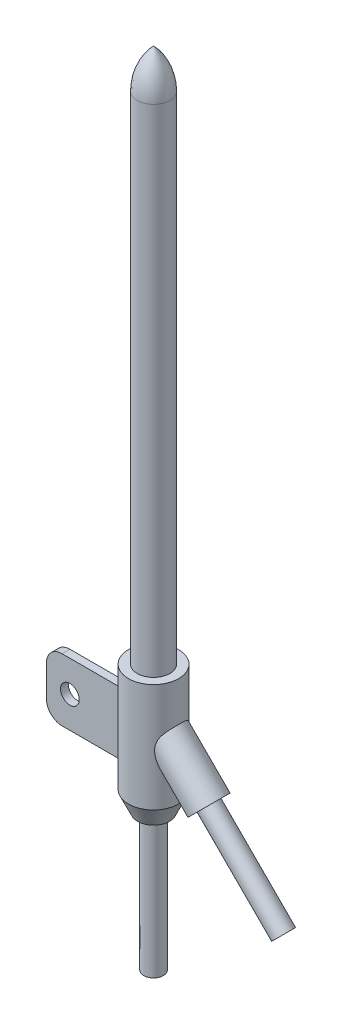
SolidWorks part; units mm, degrees
ref_plane "Front Plane" through (0, 0, 0) normal (0, 0, 1) x (1, 0, 0)
ref_plane "Top Plane" through (0, 0, 0) normal (0, 1, 0) x (1, 0, 0)
ref_plane "Right Plane" through (0, 0, 0) normal (1, 0, 0) x (0, 0, -1)
sketch "Sketch2" plane through (0, 0, 0) normal (0, 1, 0) x (1, 0, 0)
  circle A0 centre (0, 0) radius 2.085
  dimension "D1" = 4.17
extrude "Boss-Extrude1" add sketch "Sketch2" along normal blind 63.5
sketch "Sketch3" plane through (0, 0, 0) normal (0, 0, 1) x (1, 0, 0)
  line L0 (2.085, 63.5) -> (2.085, 60.967) construction
  line L1 (2.085, 0) -> (2.085, 63.5) construction
  line L2 (0, 63.5) -> (0, 68.5)
  line L3 (2.085, 63.5) -> (-2.085, 63.5) construction
  line L4 (2.085, 63.5) -> (0, 63.5)
  arc A0 (2.085, 63.5) -> (0, 68.5) centre (-4.9527, 63.5) ccw
  dimension "D1" = 5
revolve "Revolve2" add sketch "Sketch3" angle 360 about L2
sketch "Sketch4" plane through (0, 0, 0) normal (0, 0, 1) x (1, 0, 0)
  line L0 (0, 0) -> (0, -16.4)
  line L1 (0, -16.4) -> (2.05, -16.4)
  line L2 (2.05, -16.4) -> (3.21, -13.9)
  line L3 (3.21, -13.9) -> (3.21, 0)
  line L4 (3.21, 0) -> (0, 0)
  line L5 (0, 0) -> (0, -13.3708) construction
  dimension "D1" = 6.42
  dimension "D2" = 4.1
  dimension "D3" = 2.5
  dimension "D4" = 16.4
revolve "Revolve3" add sketch "Sketch4" angle 360 about L5
sketch "Sketch5" plane through (0, 0, 0) normal (0, 0, 1) x (1, 0, 0)
  line L0 (0, 0) -> (0, -16.4) construction
  line L1 (-2.05, -16.4) -> (2.05, -16.4) construction
  line L2 (0, -8.2) -> (3.21, -8.2) construction
  line L3 (3.21, -13.9) -> (3.21, 0) construction
  line L4 (0, -8.2) -> (-3.21, -8.2) construction
  line L5 (-3.21, 0) -> (-3.21, -13.9) construction
  point P13 (-3.21, -8.2)
  point P14 (3.21, -8.2)
ref_plane "Plane2" through (0, -8.2, 0) normal (0, 1, 0) x (1, 0, 0)
sketch "Sketch6" plane through (0, -8.2, 0) normal (0, 1, 0) x (1, 0, 0)
  line L0 (3.21, -6.2703) -> (3.21, 6.2703) construction
  point P2 (3.21, 0)
ref_plane "Plane3" through (5.705, -5.705, 0) normal (-0.7071, 0.7071, 0) x (0, 0, -1)
sketch "Sketch7" plane through (5.705, -5.705, 0) normal (-0.7071, 0.7071, 0) x (0, 0, -1)
  circle A0 centre (0, 3.5285) radius 2.2
  dimension "D1" = 4.4
extrude "Boss-Extrude2" add sketch "Sketch7" against normal blind 5.5 and the other way up to next
sketch "Sketch8" plane through (9.5941, -9.5941, 0) normal (0.7071, -0.7071, 0) x (0, 0, -1)
  circle A0 centre (0, -3.5285) radius 1.25
  circle A1 centre (0, -3.5285) radius 2.2 construction
  dimension "D1" = 2.5
extrude "Boss-Extrude3" add sketch "Sketch8" along normal blind 13.5
sketch "Sketch9" plane through (0, -16.4, 0) normal (0, -1, 0) x (1, 0, 0)
  circle A0 centre (0, 0) radius 1.25
  circle A1 centre (0, 0) radius 2.05 construction
  dimension "D1" = 2.5
extrude "Boss-Extrude4" add sketch "Sketch9" along normal blind 17.5
ref_plane "Plane4" through (-3.21, 0, 0) normal (1, 0, 0) x (0, 0, -1)
sketch "Sketch10" plane through (-3.21, 0, 0) normal (1, 0, 0) x (0, 0, -1)
  line L1 (0.5, -12.2) -> (-0.5, -12.2)
  line L2 (0.5, -12.2) -> (0.5, -4.2)
  line L3 (0.5, -4.2) -> (-0.5, -4.2)
  line L4 (-0.5, -12.2) -> (-0.5, -4.2)
  line L5 (0.5, -12.2) -> (-0.5, -4.2) construction
  line L6 (0.5, -4.2) -> (-0.5, -12.2) construction
  point P0 (0, -8.2)
  dimension "D1" = 8
  dimension "D2" = 1
extrude "Boss-Extrude5" add sketch "Sketch10" against normal blind 10 and the other way up to surface other way up to face at (0, 0, 3.21)
hole_wizard "M2 Clearance Hole1" positions "Sketch11" profile "Sketch12" hole size "M2" standard "ANSI Metric" end condition through all
sketch "Sketch11" plane through (0, 0, 0.5) normal (0, 0, 1) x (1, 0, 0)
  line L0 (-13.21, -8.2) -> (-10.21, -8.2) construction
  line L1 (-13.21, -4.2) -> (-13.21, -12.2) construction
  point P2 (-10.21, -8.2)
  dimension "D1" = 3
sketch "Sketch12" plane through (-10.21, -8.2, 0.5) normal (1, 0, 0) x (0, -1, 0)
  line L0 (0, 0) -> (0, 3.71)
  line L1 (0, 3.71) -> (1.2, 3.71)
  line L2 (1.2, 3.71) -> (1.2, 0)
  line L5 (1.2, 0) -> (0, 0)
  line L11 (0, -6.35) -> (0, 107.95) construction
  dimension "Thru Hole Dia." = 2.4
  dimension "Thru Hole Depth" = 3.71
fillet "Fillet1" radius 2 2 edges at (-13.21, -12.2, 0) (-13.21, -4.2, 0)
